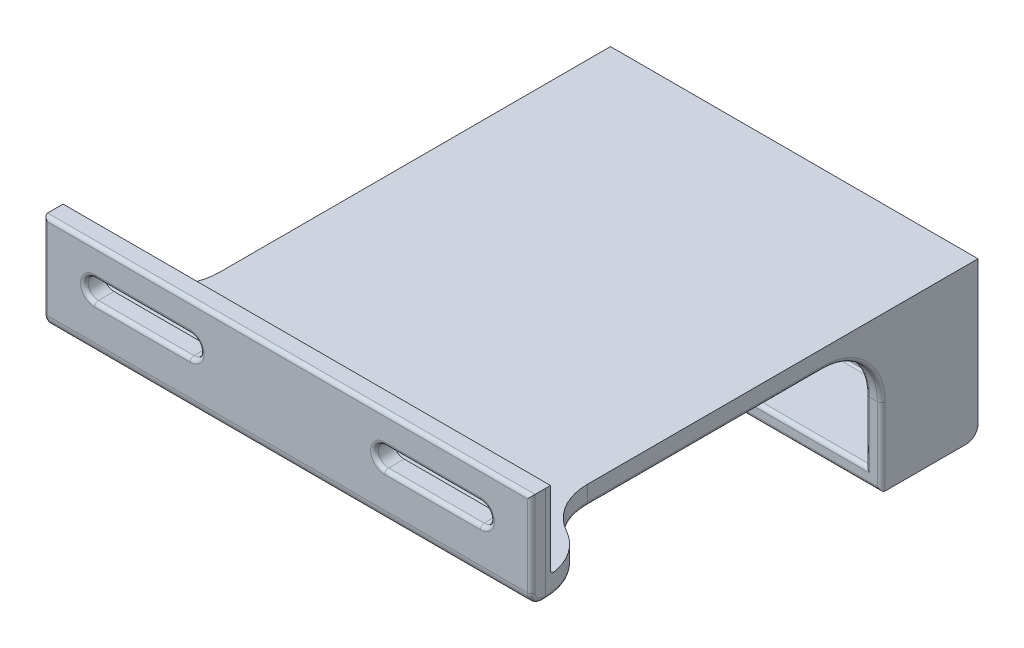
SolidWorks part; units mm, degrees
ref_plane "Alzado" through (0, 0, 0) normal (0, 0, 1) x (1, 0, 0)
ref_plane "Planta" through (0, 0, 0) normal (0, 1, 0) x (1, 0, 0)
ref_plane "Vista lateral" through (0, 0, 0) normal (1, 0, 0) x (0, 0, -1)
sketch "Sketch2" plane through (0, 0, 0) normal (0, 0, 1) x (1, 0, 0)
  line L1 (-64.9767, -9.7) -> (61.0233, -9.7)
  line L2 (-64.9767, -9.7) -> (-64.9767, 10.3)
  line L3 (-64.9767, 10.3) -> (61.0233, 10.3)
  line L4 (61.0233, -9.7) -> (61.0233, 10.3)
  line L8 (-64.9767, -9.7) -> (61.0233, -9.7)
  line L9 (-64.9767, -9.7) -> (-64.9767, -14.7)
  line L10 (-64.9767, -14.7) -> (61.0233, -14.7)
  line L11 (61.0233, -9.7) -> (61.0233, -14.7)
  dimension "D1" = 126
  dimension "D2" = 20
  dimension "D6" = 5
extrude "Boss-Extrude1" add sketch "Sketch2" along normal blind 5 contours L1 L4 L3 L2 | L11 L1 L9 L10 region at (-1.9767, 0.3, 0) region at (-1.9767, -12.2, 0)
sketch "Sketch3" plane through (0, 0, 0) normal (0, 0, -1) x (-1, 0, 0)
  line L0 (27.1267, -0.05) -> (51.8267, -0.05) construction
  line L1 (27.1267, 2.6) -> (51.8267, 2.6)
  line L2 (27.1267, -2.7) -> (51.8267, -2.7)
  line L3 (-23.1733, -0.05) -> (-47.8733, -0.05) construction
  line L4 (-23.1733, -2.7) -> (-47.8733, -2.7)
  line L5 (-23.1733, 2.6) -> (-47.8733, 2.6)
  line L6 (64.9767, -9.7) -> (-61.0233, -9.7) construction
  line L7 (-61.0233, -9.7) -> (-61.0233, 10.3) construction
  line L8 (64.9767, -9.7) -> (64.9767, 10.3) construction
  arc A0 (27.1267, 2.6) -> (27.1267, -2.7) centre (27.1267, -0.05) ccw
  arc A1 (51.8267, -2.7) -> (51.8267, 2.6) centre (51.8267, -0.05) ccw
  arc A2 (-23.1733, -2.7) -> (-23.1733, 2.6) centre (-23.1733, -0.05) ccw
  arc A3 (-47.8733, 2.6) -> (-47.8733, -2.7) centre (-47.8733, -0.05) ccw
  point P1 (39.4767, -0.05)
  point P7 (54.4767, -0.05)
  point P8 (24.4767, -0.05)
  point P11 (-35.5233, -0.05)
  point P18 (-50.5233, -0.05)
  point P19 (-20.5233, -0.05)
  dimension "D1" = 30
  dimension "D2" = 5.3
  dimension "D3" = 7
  dimension "D4" = 30
  dimension "D5" = 5.3
  dimension "D6" = 10.5
  dimension "D7" = 10.5
extrude "Cut-Extrude1" cut sketch "Sketch3" against normal blind 5
sketch "Sketch4" plane through (0, 0, 0) normal (0, 0, -1) x (-1, 0, 0)
  line L1 (64.9767, -14.7) -> (-61.0233, -14.7)
  line L2 (64.9767, -14.7) -> (64.9767, -9.7)
  line L3 (64.9767, -9.7) -> (-61.0233, -9.7)
  line L4 (-61.0233, -14.7) -> (-61.0233, -9.7)
extrude "Boss-Extrude3" add sketch "Sketch4" along normal blind 10
sketch "Sketch5" plane through (0, 0, -10) normal (0, 0, -1) x (-1, 0, 0)
  line L0 (64.9767, -14.7) -> (49.4767, -14.0849) construction
  line L1 (-61.0233, -14.7) -> (-45.5233, -14.0849) construction
  line L2 (64.9767, -14.7) -> (-61.0233, -14.7) construction
  line L3 (49.4767, -9.7) -> (-45.5233, -9.7)
  line L4 (49.4767, -9.7) -> (49.4767, -14.7)
  line L5 (49.4767, -14.7) -> (-45.5233, -14.7)
  line L6 (-45.5233, -9.7) -> (-45.5233, -14.7)
  line L9 (49.4767, -10.3151) -> (64.9767, -9.7) construction
  line L10 (-45.5233, -10.3151) -> (-61.0233, -9.7) construction
  point P8 (1.9767, -12.2)
  dimension "D1" = 95
extrude "Boss-Extrude4" add sketch "Sketch5" along normal blind 116
sketch "Sketch6" plane through (0, -14.7, 0) normal (0, -1, 0) x (1, 0, 0)
  line L6 (-49.4767, -126) -> (45.5233, -126)
  line L8 (-49.4767, -126) -> (-49.4767, -122)
  line L10 (-49.4767, -126) -> (-49.4767, -10) construction
  line L12 (-49.4767, -122) -> (45.5233, -122)
  line L13 (45.5233, -126) -> (45.5233, -10) construction
  line L14 (45.5233, -122) -> (45.5233, -126)
  dimension "D1" = 4
extrude "Boss-Extrude5" add sketch "Sketch6" along normal blind 35
sketch "Sketch7" plane through (0, 0, -122) normal (0, 0, 1) x (1, 0, 0)
  line L0 (-49.4767, -30.7) -> (-49.4767, -49.7)
  line L1 (-49.4767, -49.7) -> (-49.4767, -14.7) construction
  line L2 (-49.4767, -49.7) -> (45.5233, -49.7)
  line L3 (45.5233, -49.7) -> (45.5233, -14.7)
  line L4 (45.5233, -14.7) -> (41.5233, -14.7)
  line L5 (-64.9767, -14.7) -> (61.0233, -14.7) construction
  line L6 (41.5233, -14.7) -> (41.5233, -45.7)
  line L7 (41.5233, -45.7) -> (-45.4767, -45.7)
  line L8 (-45.4767, -45.7) -> (-45.4767, -30.7)
  line L9 (-45.4767, -30.7) -> (-49.4767, -30.7)
  dimension "D1" = 19
  dimension "D2" = 4
  dimension "D3" = 4
  dimension "D4" = 4
extrude "Boss-Extrude6" add sketch "Sketch7" along normal blind 21
fillet "Fillet2" radius 15 2 edges at (-49.4767, -12.2, -10) (45.5233, -12.2, -10)
fillet "Fillet3" radius 15 2 edges at (61.0233, -12.2, -10) (-64.9767, -12.2, -10)
fillet "Fillet4" radius 3 1 edges at (-1.9767, -49.7, -126)
fillet "Fillet5" radius 15 1 edges at (43.5233, -14.7, -101)
fillet "Fillet6" radius 0.5 5 edges at (41.5233, -30.2, -122) (-1.9767, -45.7, -122) (-45.4767, -38.2, -122) (-47.4767, -30.7, -122) (-3.9767, -14.7, -122)
fillet "Fillet7" radius 3 1 edges at (-1.9767, -14.7, 5)
fillet "Fillet8" radius 1 1 edges at (-1.9767, -9.7, 0)
fillet "Fillet9" radius 1 34 edges at (-49.4767, -30.7, -111.25) (-49.4767, -30.5536, -121.8536) (-49.4767, -22.7, -122) (-49.4767, -14.8464, -121.8536) (-49.4767, -14.7, -73.25) (-51.5587, -14.7, -17.376) (-62.8947, -14.7, -6.3609) (-64.9767, -14.7, 1.6315) (-64.9767, -13.8213, 4.1213) (41.5233, -19.0934, -96.6066) (61.0233, -13.8213, 4.1213) (61.0233, -14.7, 1.6315) (58.9413, -14.7, -6.3609) (47.6053, -14.7, -17.376) (45.5233, -14.7, -55.5) (45.5233, -19.0934, -96.6066) (-1.9767, 10.3, 5) (61.0233, -0.7, 5) (-64.9767, -0.7, 5) (35.5233, -2.7, 5) (50.5233, -0.05, 5) (35.5233, 2.6, 5) (20.5233, -0.05, 5) (-39.4767, 2.6, 5) (-54.4767, -0.05, 5) (-39.4767, -2.7, 5) (-24.4767, -0.05, 5) (41.5233, -37.7, -101) (45.5233, -39.7, -101) (-1.9767, -49.7, -101) (-49.4767, -40.2, -101) (-47.4767, -30.7, -101) (-45.4767, -38.2, -101) (-1.9767, -45.7, -101)
sketch "Sketch8" plane through (0, -14.7, 0) normal (0, -1, 0) x (-1, 0, 0)
  line L0 (7.0539, 52.0969) -> (-2.0447, 52.0969)
  line L1 (7.0539, 61.4458) -> (-2.0447, 61.4458)
  line L2 (-2.0447, 61.4458) -> (-2.0447, 52.0969)
  line L3 (7.0539, 58.891) -> (7.0539, 61.4458)
  line L4 (7.0539, 58.891) -> (0.3414, 58.891)
  line L5 (0.3414, 58.891) -> (0.3414, 54.7105)
  line L6 (0.3414, 54.7105) -> (7.0539, 54.7105)
  line L7 (7.0539, 54.7105) -> (7.0539, 52.0969)
  line L8 (-2.0447, 61.8174) -> (-2.0447, 64.558)
  line L9 (-2.0447, 64.558) -> (5.1722, 66.7411)
  line L10 (5.1722, 66.7411) -> (-2.0447, 68.9243)
  line L11 (-2.0447, 68.9243) -> (-2.0447, 71.3862)
  line L12 (-2.0447, 71.3862) -> (7.0539, 68.6338)
  line L13 (7.0539, 68.6338) -> (7.0539, 64.558)
  line L14 (7.0539, 64.558) -> (-2.0447, 61.8174)
  line L15 (-2.0447, 72.6795) -> (-2.0447, 75.1474)
  line L16 (-2.0447, 75.1474) -> (7.0539, 75.1474)
  line L17 (7.0539, 75.1474) -> (7.0539, 72.6795)
  line L18 (7.0539, 72.6795) -> (-2.0447, 72.6795)
  line L19 (-2.0447, 76.8968) -> (7.0539, 76.8968)
  line L20 (7.0539, 76.8968) -> (7.0539, 85.9562)
  line L21 (7.0539, 85.9562) -> (-2.0447, 85.9562)
  line L22 (-2.0447, 85.9562) -> (-2.0447, 76.8968)
  line L23 (5.1722, 79.4584) -> (0, 79.4584)
  line L24 (0, 79.4584) -> (0, 81.4265)
  line L25 (5.1722, 79.4584) -> (5.1722, 81.4265)
  line L26 (-2.1598, 87.2147) -> (-2.1598, 89.8404)
  line L27 (-2.1598, 89.8404) -> (7.0539, 89.8404)
  line L28 (7.0539, 89.8404) -> (7.0539, 87.2147)
  line L29 (7.0539, 87.2147) -> (-2.1598, 87.2147)
  line L30 (7.0539, 90.8586) -> (-2.1598, 94.5918)
  line L31 (-2.1598, 94.5918) -> (-2.1598, 98.1464)
  line L32 (-2.1598, 98.1464) -> (7.0539, 101.7545)
  line L33 (7.0539, 101.7545) -> (7.0539, 98.9323)
  line L34 (7.0539, 98.9323) -> (5.5274, 98.3345)
  line L35 (5.5274, 98.3345) -> (5.5274, 94.0738)
  line L36 (5.5274, 94.0738) -> (7.0539, 93.4553)
  line L37 (7.0539, 93.4553) -> (7.0539, 90.8586)
  line L38 (3.842, 94.5918) -> (-0.397, 96.3093)
  line L39 (-0.397, 96.3093) -> (3.842, 97.9694)
  line L40 (3.842, 97.9694) -> (3.842, 94.5918)
  line L41 (-2.9505, 33.5253) -> (-4.8951, 33.5253)
  line L42 (-4.8951, 33.5253) -> (-4.8951, 47.6239)
  line L43 (-4.8951, 47.6239) -> (10.1516, 47.6239)
  line L44 (10.1516, 47.6239) -> (10.1516, 33.5253)
  line L45 (10.1516, 33.5253) -> (8.4014, 33.5253)
  line L46 (0.7687, 33.5253) -> (-0.5602, 33.5253)
  line L47 (2.9166, 35.9656) -> (1.4639, 37.836)
  line L48 (3.1022, 43.443) -> (4.5364, 45.971)
  line L49 (8.4014, 33.5253) -> (-2.9505, 33.5253)
  arc A0 (5.1722, 81.4265) -> (0, 81.4265) centre (2.5861, 80.5802) ccw
  arc A1 (1.3521, 24.9931) -> (-2.9505, 33.5253) centre (11.6001, 35.5118) cw
  arc A2 (8.4014, 33.5253) -> (1.3521, 24.9931) centre (-1.5824, 34.5958) cw
  arc A3 (8.4014, 33.5253) -> (4.5364, 45.971) centre (-9.9612, 34.6458) ccw
  arc A4 (7.2346, 33.5253) -> (3.1022, 43.443) centre (-5.3196, 34.1141) ccw
  arc A5 (-0.5602, 33.5253) -> (1.4639, 29.0771) centre (6.6714, 34.1313) ccw
  arc A6 (-0.5602, 33.5253) -> (1.4639, 37.836) centre (3.3994, 34.2966) cw
  arc A7 (2.9166, 35.9656) -> (0.7687, 33.5253) centre (3.8862, 32.9468) ccw
  arc A8 (5.8731, 33.5253) -> (1.1017, 42.3863) centre (-4.4588, 33.6771) ccw
  arc A9 (-1.7049, 33.5253) -> (1.3521, 39.9577) centre (5.2937, 34.1418) cw
  arc A10 (1.3521, 39.9577) -> (4.6391, 35.7234) centre (-3.1166, 33.0957) cw
  arc A11 (4.6391, 35.7234) -> (4.6391, 33.5253) centre (2.0694, 34.6243) cw
  arc A12 (1.1017, 42.3863) -> (-2.9505, 33.5253) centre (6.9776, 34.3422) ccw
  arc A13 (5.8731, 33.5253) -> (1.4639, 29.0771) centre (0.008, 34.9296) cw
  arc A14 (-1.7049, 33.5253) -> (1.6733, 27.3593) centre (6.3674, 33.9395) ccw
  arc A15 (1.6733, 27.3593) -> (7.2346, 33.5253) centre (-0.6179, 35.0168) ccw
  arc A16 (0.7687, 33.5253) -> (1.6733, 31.0711) centre (4.2971, 33.432) ccw
  arc A17 (4.5364, 33.5253) -> (1.6733, 31.0711) centre (0.0907, 35.8146) cw
  point P86 (0, 0)
  point P87 (1.8045, 30.6256)
  point P88 (1.6733, 31.0711)
  point P89 (0, 0)
